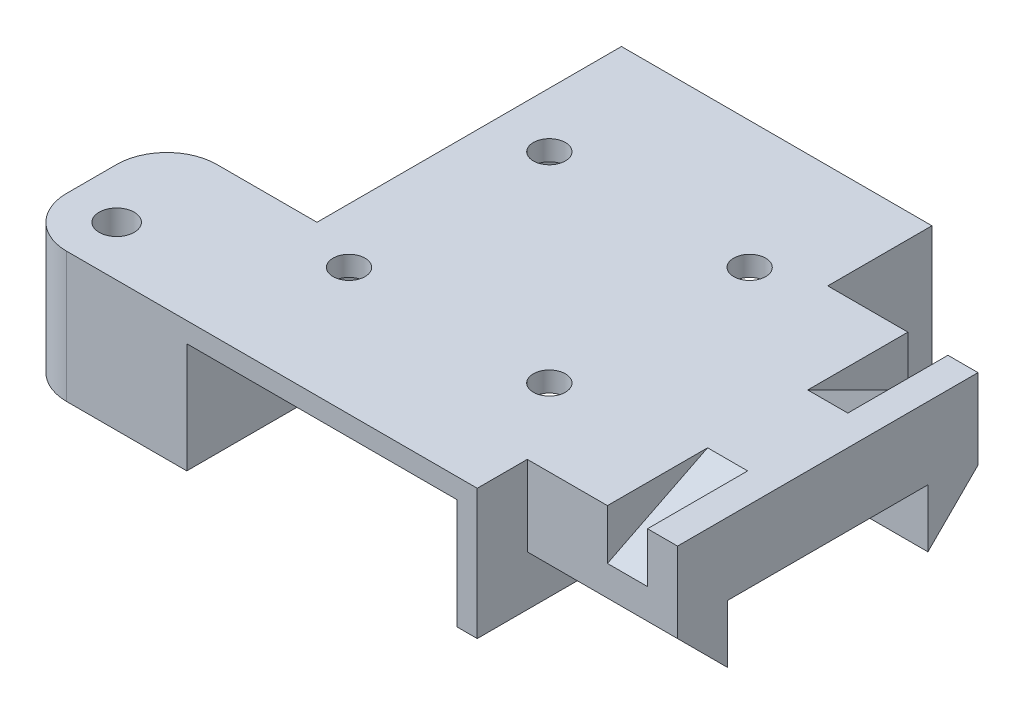
SolidWorks part; units mm, degrees
ref_plane "Front Plane" through (0, 0, 0) normal (0, 0, 1) x (1, 0, 0)
ref_plane "Top Plane" through (0, 0, 0) normal (0, 1, 0) x (1, 0, 0)
ref_plane "Right Plane" through (0, 0, 0) normal (1, 0, 0) x (0, 0, -1)
sketch "Sketch1" plane through (0, 0, 0) normal (0, 1, 0) x (1, 0, 0)
  line L1 (0, 0) -> (31, 0)
  line L2 (0, 0) -> (0, 45.4)
  line L3 (0, 45.4) -> (31, 45.4)
  line L4 (31, 0) -> (31, 45.4)
  dimension "D1" = 31
  dimension "D2" = 45.4
extrude "Boss-Extrude1" add sketch "Sketch1" along normal blind 13
sketch "Sketch2" plane through (0, 0, 0) normal (0, 0, 1) x (1, 0, 0)
  line L0 (0, 0) -> (31, 0) construction
  line L1 (2, 0) -> (29, 0)
  line L2 (2, 0) -> (2, 11)
  line L3 (2, 11) -> (29, 11)
  line L4 (29, 0) -> (29, 11)
  line L5 (0, 13) -> (0, 0) construction
  line L6 (31, 13) -> (31, 0) construction
  line L7 (0, 13) -> (31, 13) construction
  dimension "D1" = 2
  dimension "D2" = 2
  dimension "D3" = 2
extrude "Cut-Extrude1" cut sketch "Sketch2" against normal through all
sketch "Sketch3" plane through (0, 13, 0) normal (0, 1, 0) x (1, 0, 0)
  line L0 (15.5, 45.4) -> (15.5, 0) construction
  line L5 (5.5, 12.7) -> (25.5, 12.7) construction
  line L6 (5.5, 12.7) -> (5.5, 32.7) construction
  line L7 (5.5, 32.7) -> (25.5, 32.7) construction
  line L8 (25.5, 12.7) -> (25.5, 32.7) construction
  line L9 (5.5, 12.7) -> (25.5, 32.7) construction
  line L10 (5.5, 32.7) -> (25.5, 12.7) construction
  line L11 (31, 45.4) -> (0, 45.4) construction
  line L12 (0, 0) -> (31, 0) construction
  line L13 (0, 22.7) -> (31, 22.7) construction
  line L14 (0, 45.4) -> (0, 0) construction
  line L15 (31, 0) -> (31, 45.4) construction
  circle A0 centre (5.5, 32.7) radius 1.6
  circle A1 centre (25.5, 32.7) radius 1.6
  circle A2 centre (25.5, 12.7) radius 1.6
  circle A3 centre (5.5, 12.7) radius 1.6
  point P0 (15.5, 22.7)
  dimension "D3" = 3.2
  dimension "D1" = 20
  dimension "D2" = 20
extrude "Cut-Extrude2" cut sketch "Sketch3" against normal blind 10
sketch "Sketch4" plane through (0, 0, 0) normal (-1, 0, 0) x (0, 0, 1)
  line L0 (-45.4, 13) -> (0, 13) construction
  line L1 (-15, 13) -> (0, 13)
  line L2 (-15, 13) -> (-15, 0)
  line L3 (-15, 0) -> (0, 0)
  line L4 (0, 13) -> (0, 0)
  dimension "D1" = 15
extrude "Boss-Extrude2" add sketch "Sketch4" along normal blind 15
sketch "Sketch5" plane through (0, 13, 0) normal (0, 1, 0) x (1, 0, 0)
  line L2 (-15, 0) -> (31, 0) construction
  line L3 (0, 45.4) -> (0, 15) construction
  circle A0 centre (-10, 5) radius 1.75
  dimension "D1" = 3.5
  dimension "D2" = 5
  dimension "D3" = 10
extrude "Cut-Extrude3" cut sketch "Sketch5" against normal blind 20
fillet "Fillet1" radius 5 2 edges at (-15, 6.5, -15) (-15, 6.5, 0)
sketch "Sketch6" plane through (31, 0, 0) normal (1, 0, 0) x (0, 0, -1)
  line L9 (5, 0) -> (10, 0)
  line L10 (0, 0) -> (45.4, 0) construction
  line L11 (10, 0) -> (10, 5.8)
  line L12 (10, 5.8) -> (30, 5.8)
  line L13 (30, 5.8) -> (30, 0)
  line L14 (30, 0) -> (35, 0)
  line L15 (35, 0) -> (35, 13)
  line L16 (35, 13) -> (5, 13)
  line L17 (5, 13) -> (5, 0)
  line L18 (0, 13) -> (45.4, 13) construction
  line L19 (0, 13) -> (0, 0) construction
  dimension "D1" = 5
  dimension "D2" = 5
  dimension "D3" = 5.8
  dimension "D4" = 20
  dimension "D5" = 5
extrude "Boss-Extrude3" add sketch "Sketch6" along normal blind 15
chamfer "Chamfer1" distance 5 angle 45 2 edges at (38.5, 0, -5) (38.5, 0, -35)
ref_plane "Plane1" through (43, 0, 0) normal (1, 0, 0) x (0, 0, -1)
sketch "Sketch7" plane through (43, 0, 0) normal (1, 0, 0) x (0, 0, -1)
  line L0 (5, 8) -> (15, 13)
  line L1 (5, 13) -> (5, 5) construction
  line L3 (15, 13) -> (5, 13)
  line L4 (5, 13) -> (5, 8)
  line L5 (35, 8) -> (25, 13)
  line L6 (35, 5) -> (35, 13) construction
  line L7 (25, 13) -> (35, 13)
  line L8 (35, 13) -> (35, 8)
  line L9 (35, 13) -> (5, 13) construction
  dimension "D1" = 5
  dimension "D2" = 5
  dimension "D3" = 10
  dimension "D4" = 10
extrude "Cut-Extrude4" cut sketch "Sketch7" against normal blind 4
mirror "Mirror1" [suppressed] of bodies 111 105
delete or keep bodies "Body-Delete/Keep 1" [suppressed] type delete bodies bodies 111
mirror "Mirror2" [suppressed] of bodies 105
mirror "Mirror3" [suppressed] of bodies 107
delete or keep bodies "Body-Delete/Keep 2" [suppressed] type delete bodies bodies 105 107
mirror "Mirror4" [suppressed] of bodies 111 105
delete or keep bodies "Body-Delete/Keep 3" [suppressed] type delete bodies bodies 111
sketch "Sketch10" [suppressed] plane through (46, 0, 0) normal (1, 0, 0) x (0, 0, -1)
  line L0 (60.8, 12) -> (85.8, 12) construction
  line L1 (80.8, 12) -> (85.8, 12)
  line L2 (80.8, 12) -> (80.8, -14.5)
  line L3 (80.8, -14.5) -> (85.8, -14.5)
  line L4 (85.8, 12) -> (85.8, -14.5)
  line L5 (80.8, 0) -> (80.8, 4.7) construction
  line L6 (85.8, 12) -> (85.8, 5) construction
  dimension "D1" = 26.5
extrude "Boss-Extrude7" [suppressed] add sketch "Sketch10" along normal blind 2
sketch "Sketch11" [suppressed] plane through (46, 0, 0) normal (-1, 0, 0) x (0, 0, 1)
  line L0 (-80.8, 0) -> (-80.8, -14.5) construction
  line L1 (-85.8, -14.5) -> (-80.8, -14.5)
  line L2 (-85.8, -14.5) -> (-85.8, -13)
  line L3 (-85.8, -13) -> (-80.8, -13)
  line L4 (-80.8, -14.5) -> (-80.8, -13)
  dimension "D1" = 1.5
extrude "Boss-Extrude8" [suppressed] add sketch "Sketch11" along normal blind 10
fillet "Fillet2" [suppressed] radius 7.5
